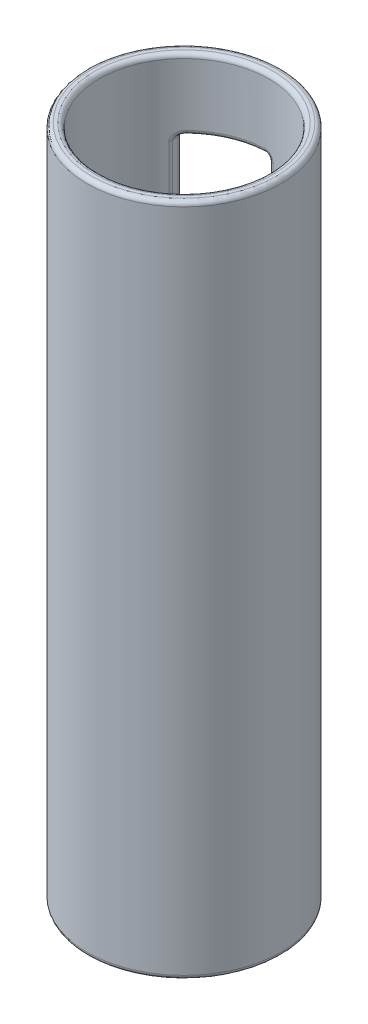
SolidWorks part; units mm, degrees
ref_plane "Front Plane" through (0, 0, 0) normal (0, 0, 1) x (1, 0, 0)
ref_plane "Top Plane" through (0, 0, 0) normal (0, 1, 0) x (1, 0, 0)
ref_plane "Right Plane" through (0, 0, 0) normal (1, 0, 0) x (0, 0, -1)
sketch "Sketch1" plane through (0, 0, 0) normal (0, 1, 0) x (1, 0, 0)
  circle A0 centre (0, 0) radius 22
  dimension "D1" = 44
extrude "Boss-Extrude1" add sketch "Sketch1" along normal blind 153
sketch "Sketch2" plane through (0, 153, 0) normal (0, 1, 0) x (1, 0, 0)
  circle A0 centre (0, 0) radius 19.25
  dimension "D1" = 38.5
extrude "Cut-Extrude1" cut sketch "Sketch2" against normal blind 155
sketch "Sketch3" plane through (0, 0, 0) normal (0, 0, 1) x (1, 0, 0)
  line L0 (0, 0) -> (0, 33.7672) construction
  line L2 (0, 16.8836) -> (-15, 16.8836)
  line L3 (0, 16.8836) -> (0, 136.8836)
  line L4 (0, 136.8836) -> (-15, 136.8836)
  line L5 (-15, 16.8836) -> (-15, 136.8836)
  dimension "D1" = 120
  dimension "D2" = 15
extrude "Cut-Extrude2" cut sketch "Sketch3" against normal blind 150
fillet "Fillet1" radius 1 16 edges at (0, 153, 22) (0, 153, 19.25) (0, 0, 22) (0, 0, 19.25) (-8.0605, 136.8836, -20.4702) (-8.316, 136.8836, -17.3611) (-15, 76.8836, -16.0935) (-15, 76.8836, -12.0649) (-15, 136.8836, -14.0792) (-8.0605, 16.8836, -20.4702) (-8.316, 16.8836, -17.3611) (-15, 16.8836, -14.0792) (0, 76.8836, -22) (0, 136.8836, -20.625) (0, 76.8836, -19.25) (0, 16.8836, -20.625)
